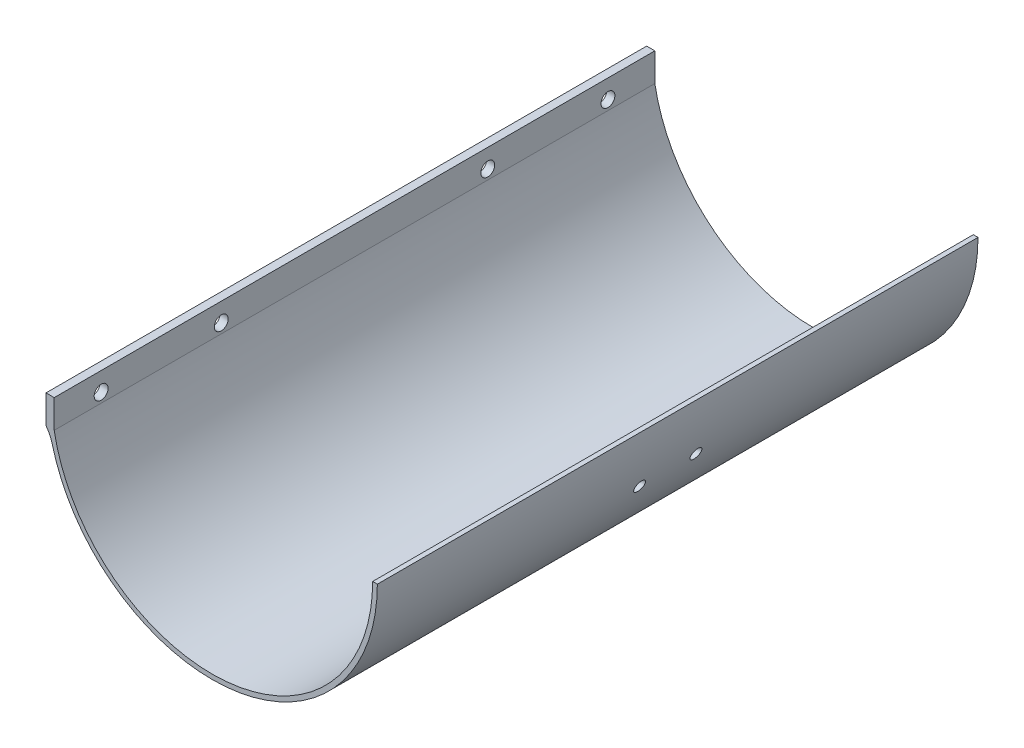
SolidWorks part; units mm, degrees
ref_plane "Front Plane" through (0, 0, 0) normal (0, 0, 1) x (1, 0, 0)
ref_plane "Top Plane" through (0, 0, 0) normal (0, 1, 0) x (1, 0, 0)
ref_plane "Right Plane" through (0, 0, 0) normal (1, 0, 0) x (0, 0, -1)
sketch "Sketch1" plane through (0, 0, 0) normal (0, 0, 1) x (1, 0, 0)
  line L0 (-44, 0) -> (-42.75, 0)
  line L1 (42.75, 0) -> (44, 0)
  arc A0 (-44, 0) -> (44, 0) centre (0, 0) ccw
  arc A1 (-42.75, 0) -> (42.75, 0) centre (0, 0) ccw
  dimension "D1" = 88
  dimension "D2" = 85.5
extrude "Boss-Extrude1" add sketch "Sketch1" along normal blind 160
sketch "Sketch2" plane through (0, 0, 0) normal (1, 0, 0) x (0, 0, -1)
  line L0 (-160, 0) -> (-160, -44) construction
  line L2 (-160, 0) -> (0, 0) construction
  circle A0 centre (-147.5, -5) radius 1.85
  circle A1 centre (-115.5, -5) radius 1.85
  circle A2 centre (-44.5, -5) radius 1.85
  circle A3 centre (-12.5, -5) radius 1.85
  dimension "D1" = 3.7
  dimension "D2" = 3.7
  dimension "D3" = 3.7
  dimension "D4" = 3.7
  dimension "D5" = 32
  dimension "D6" = 32
  dimension "D7" = 71
  dimension "D8" = 12.5
  dimension "D10" = 5
extrude "Cut-Extrude1" cut sketch "Sketch2" against normal up to surface (43.715 mm away) up to face at (0, -22, 80)
ref_plane "Plane1" through (0, 0, 72) normal (0, 0, -1) x (-1, 0, 0)
sketch "Sketch4" plane through (0, 0, 72) normal (0, 0, -1) x (-1, 0, 0)
  line L0 (-42.1884, 12.4954) -> (-40.8831, 12.4954)
  line L1 (-44, 0) -> (-42.75, 0)
  arc A0 (-40.8831, 12.4954) -> (-42.75, 0) centre (0, 0) ccw
  arc A1 (-42.1884, 12.4954) -> (-44, 0) centre (0, 0) ccw
  dimension "D1" = 88
  dimension "D2" = 85.5
extrude "Boss-Extrude2" add sketch "Sketch4" along normal blind 7.5 and the other way blind 7.5
sketch "Sketch5" plane through (0, 0, 160) normal (0, 0, 1) x (1, 0, 0)
  line L5 (-44, 0) -> (-44, -7.5543)
  line L6 (-44, -7.5543) -> (-42.7628, -7.5543)
  line L7 (-42.7628, -7.5543) -> (-42.7628, 0)
  line L8 (-42.75, 0) -> (-44, 0) construction
  line L9 (-42.7628, 0) -> (-44, 0)
extrude "Cut-Extrude2" cut sketch "Sketch5" against normal up to surface (160 mm away) up to face at (0, -21.6875, 0)
sketch "Sketch6" plane through (-42.7628, 0, 0) normal (-1, 0, 0) x (0, 0, 1)
  line L1 (0, -7.5543) -> (160, -7.5543)
  line L2 (0, -7.5543) -> (0, 0)
  line L3 (0, 0) -> (160, 0)
  line L4 (160, -7.5543) -> (160, 0)
  circle A0 centre (12.5, -5) radius 1.5
  circle A1 centre (44.5, -5) radius 1.5
  circle A2 centre (115.5, -5) radius 1.5
  circle A3 centre (147.5, -5) radius 1.5
  circle M5 centre (44.5, -5) radius 1.85
  circle M6 centre (147.5, -5) radius 1.85
  line M7 (0, 0) -> (0, -7.5543)
  line M8 (0, -7.5543) -> (160, -7.5543)
  line M9 (160, -7.5543) -> (160, 0)
  line M10 (160, 0) -> (0, 0)
  circle M11 centre (115.5, -5) radius 1.85
  circle M12 centre (12.5, -5) radius 1.85
extrude "Boss-Extrude3" add sketch "Sketch6" along normal blind 0.5 contours M10 M7 M8 M9 M6 M11 M12 M5 region at (-42.7628, -3.732, 80)
sketch "Sketch7" plane through (0, 0, 160) normal (0, 0, 1) x (1, 0, 0)
  line L0 (3.1936, -47.2716) -> (4.2473, -46.1824)
  line L2 (2.6526, -44.3202) -> (7.0646, -42.9225)
  line L3 (2.6526, -44.3202) -> (-0.0812, -45.0066)
  line L4 (-2.6526, -44.3202) -> (-7.0646, -42.9225)
  arc A1 (-0.0812, -45.0066) -> (3.1936, -47.2716) centre (-0.0812, -48.5066) ccw
  arc A2 (-2.6526, -44.3202) -> (4.2473, -46.1824) centre (-0.0812, -48.5066) ccw
  arc A3 (-7.0646, -42.9225) -> (7.0646, -42.9225) centre (0, 0) ccw
  dimension "D1" = 43.5
  dimension "D2" = 7
extrude "Boss-Extrude4" add sketch "Sketch7" against normal blind 85
fillet "Fillet3" radius 0.5 1 edges at (4.2473, -46.1824, 117.5)
sketch "Sketch9" plane through (0, 0, 0) normal (1, 0, 0) x (0, 0, -1)
  line L0 (-79.5, 12.4954) -> (-79.5, 0) construction
  line L1 (-78, 8.4954) -> (-66, 8.4954)
  line L2 (-78, 8.4954) -> (-78, 2.4954)
  line L3 (-78, 2.4954) -> (-66, 2.4954)
  line L4 (-66, 8.4954) -> (-66, 2.4954)
  line L5 (-79.5, 12.4954) -> (-64.5, 12.4954) construction
  dimension "D1" = 12
  dimension "D2" = 6
  dimension "D3" = 1.5
  dimension "D4" = 4
extrude "Cut-Extrude4" cut sketch "Sketch9" along normal up to surface (43.1721 mm away) up to face at (15.0324, -18.3013, 89.8333)
sketch "Sketch11" plane through (0, 0, 160) normal (0, 0, 1) x (1, 0, 0)
  line L1 (6.0382, -53.7585) -> (4.3409, -43.7853)
  line L2 (6.0382, -53.7585) -> (2.0015, -51.3196)
  line L3 (-6.6638, -46.7537) -> (-4.3409, -43.7853)
  line L4 (2.6526, -44.3202) -> (4.3409, -43.7853) construction
  arc A1 (-6.6638, -46.7537) -> (6.0382, -53.7585) centre (2.0015, -46.0596) ccw
  arc A2 (-4.3409, -43.7853) -> (4.3409, -43.7853) centre (0, 0) ccw
  arc A3 (-0.0812, -45.0066) -> (3.1936, -47.2716) centre (-0.0812, -48.5066) ccw construction
  arc A4 (4.3409, -43.7853) -> (44, 0) centre (0, 0) ccw construction
  dimension "D1" = 44
extrude "Cut-Extrude5" cut sketch "Sketch11" against normal blind 72 contours A1 L3 A2 L1
sketch "Sketch12" plane through (0, 0, 0) normal (0, 0, -1) x (-1, 0, 0)
  line L2 (42.75, 0) -> (42.75, -7.5543)
  line L6 (42.75, -7.5543) -> (41.523, -7.5543)
  line L7 (41.523, -7.5543) -> (42.75, 0)
extrude "Cut-Extrude6" cut sketch "Sketch12" against normal up to surface (160 mm away) up to face at (-13.7346, -16.3196, 160)
sketch "Sketch14" plane through (-43.2628, 0, 0) normal (-1, 0, 0) x (0, 0, 1)
  line L0 (0, -7.5543) -> (160, -7.5543) construction
  line L1 (0, 0) -> (160, 0)
  line L2 (0, 0) -> (0, -7.5543)
  line L3 (0, -7.5543) -> (160, -7.5543)
  line L4 (160, 0) -> (160, -7.5543)
  line L5 (160, -7.5543) -> (160, 0) construction
  circle A0 centre (12.5, -5) radius 1.85
  circle A1 centre (44.5, -5) radius 1.85
  circle A2 centre (115.5, -5) radius 1.85
  circle A3 centre (147.5, -5) radius 1.85
  dimension "D1" = 3.7
  dimension "D2" = 3.7
  dimension "D3" = 3.7
  dimension "D4" = 3.7
extrude "Boss-Extrude5" add sketch "Sketch14" along normal blind 1 and the other way blind 1.5
sketch "Sketch17" plane through (0, -7.5543, 0) normal (0, -1, 0) x (1, 0, 0)
  line L1 (-42.0773, 160) -> (-41.7628, 160)
  line L2 (-42.0773, 160) -> (-42.0773, 0)
  line L3 (-42.0773, 0) -> (-41.7628, 0)
  line L4 (-41.7628, 160) -> (-41.7628, 0)
extrude "Cut-Extrude8" cut sketch "Sketch17" against normal up to surface (7.5543 mm away) up to face at (-43.0128, 0, 80)
fillet "Fillet4" radius 10 1 edges at (-43.3467, -7.5543, 80)
sketch "Sketch18" plane through (0, 0, 79.5) normal (0, 0, 1) x (1, 0, 0)
  line L1 (40.1344, 0) -> (45.8139, 0)
  line L2 (40.1344, 0) -> (40.1344, 15.0548)
  line L3 (40.1344, 15.0548) -> (45.8139, 15.0548)
  line L4 (45.8139, 0) -> (45.8139, 15.0548)
extrude "Cut-Extrude9" cut sketch "Sketch18" against normal up to surface (15 mm away) up to face at (42.6841, 6.2814, 64.5)
sketch "Sketch19" plane through (-42.0773, 0, 0) normal (1, 0, 0) x (0, 0, -1)
  line L0 (-80, 0) -> (-80, -20.7313) construction
  line L1 (-160, 0) -> (0, 0) construction
  circle A0 centre (-87.5, -15) radius 1.5
  circle A1 centre (-72.5, -15) radius 1.5
  dimension "D1" = 3
  dimension "D2" = 3
  dimension "D3" = 15
  dimension "D4" = 7.5
  dimension "D5" = 15
extrude "Cut-Extrude10" cut sketch "Sketch19" along normal up to surface (63.4415 mm away) from offset 20 up to face at (3.1311, -24.5812, 80)
sketch "Sketch20" plane through (0, 0, 75) normal (0, 0, -1) x (-1, 0, 0)
  line L0 (4.2376, -51.1264) -> (9.3647, -42.9919)
  line L1 (2.6526, -44.3202) -> (4.3409, -43.7853)
  arc A0 (4.2376, -51.1264) -> (2.6526, -44.3202) centre (0.0812, -48.5066) ccw
  arc A3 (-44, 0) -> (42.595, -11.0303) centre (0, 0) ccw construction
  arc A4 (4.3409, -43.7853) -> (9.3647, -42.9919) centre (0, 0) ccw
  arc A5 (-4.5622, -46.9012) -> (2.6526, -44.3202) centre (0.0812, -48.5066) ccw construction
extrude "Boss-Extrude6" add sketch "Sketch20" against normal up to surface (13 mm away) up to face at (0.6422, -46.8572, 88)
